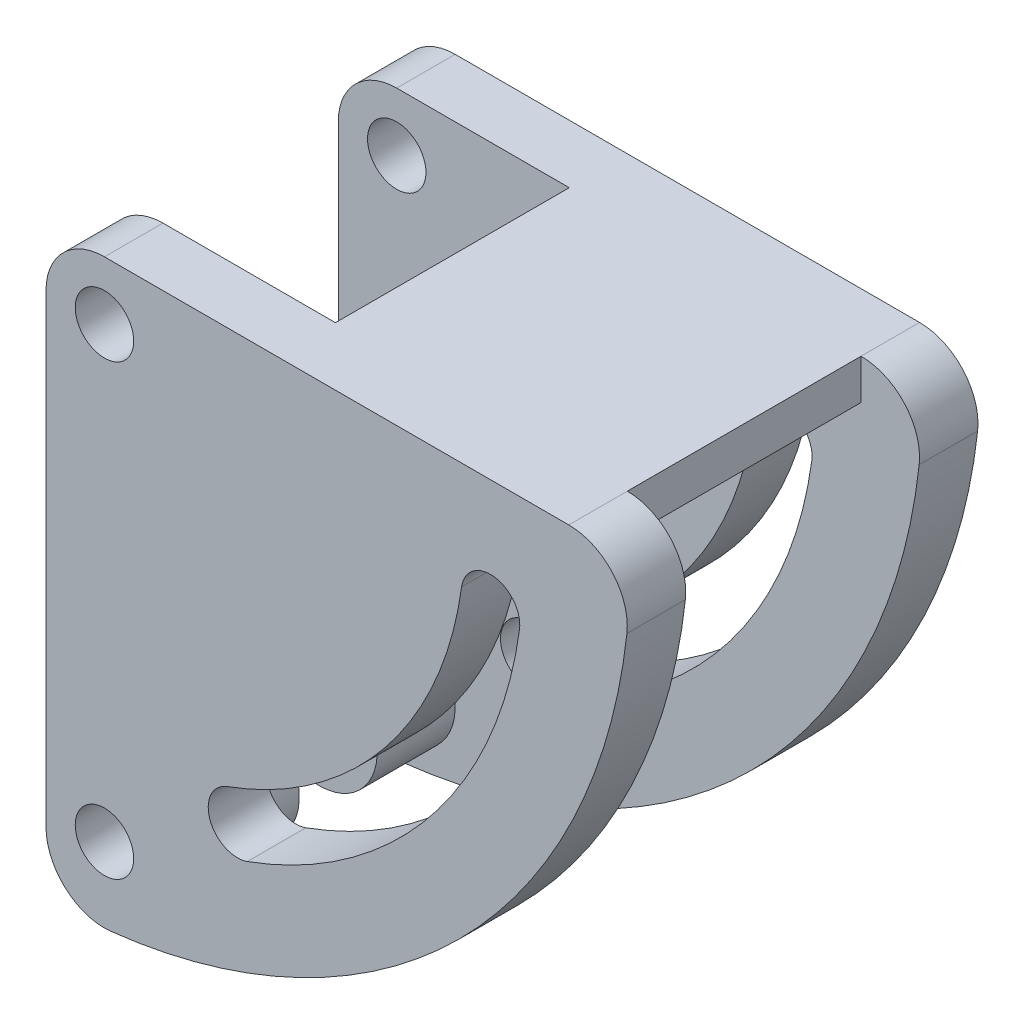
SolidWorks part; units mm, degrees
ref_plane "Front Plane" through (0, 0, 0) normal (0, 0, 1) x (1, 0, 0)
ref_plane "Top Plane" through (0, 0, 0) normal (0, 1, 0) x (1, 0, 0)
ref_plane "Right Plane" through (0, 0, 0) normal (1, 0, 0) x (0, 0, -1)
sketch "Sketch1" plane through (0, 0, 0) normal (0, 0, 1) x (1, 0, 0)
  line L0 (0, 0) -> (30, 0)
  line L1 (0, 0) -> (0, -30)
  arc A0 (0, -30) -> (30, 0) centre (0, 0) ccw
  circle A1 centre (3, -26) radius 1.5
  arc A4 (22.8157, -5.7086) -> (9.825, -21.7995) centre (3, -3) cw construction
  circle A7 centre (3, -3) radius 1.5
  arc A8 (21.3296, -5.5055) -> (9.3131, -20.3895) centre (3, -3) cw
  arc A9 (10.3369, -23.2094) -> (24.3019, -5.9118) centre (3, -3) ccw
  arc A10 (24.3019, -5.9118) -> (21.3296, -5.5055) centre (22.8157, -5.7086) ccw
  arc A11 (9.3131, -20.3895) -> (10.3369, -23.2094) centre (9.825, -21.7995) ccw
  point P7 (9.825, -21.7995)
  dimension "D2" = 3
  dimension "D3" = 3
  dimension "D8" = 30
  dimension "D1" = 20
  dimension "D4" = 3
  dimension "D5" = 3
  dimension "D6" = 4
  dimension "D7" = 3
extrude "Boss-Extrude1" add sketch "Sketch1" along normal blind 3
pattern_linear "LPattern1" count 2 spacing 15 along (0, 0, 1) of "Boss-Extrude1"
fillet "Fillet2" radius 3 3 edges at (0, -30, 1.5) (0, 0, 1.5) (30, 0, 1.5)
fillet "Fillet3" radius 3 3 edges at (0, -30, 16.5) (0, 0, 16.5) (30, 0, 16.5)
sketch "Sketch2" plane through (0, 0, 3) normal (0, 0, 1) x (1, 0, 0)
  line L0 (26.8328, 0) -> (3, 0) construction
  line L1 (11.8553, 0) -> (26.8328, 0)
  line L2 (11.8553, 0) -> (11.8553, -2.0588)
  line L3 (11.8553, -2.0588) -> (26.8328, -2.0588)
  line L4 (26.8328, 0) -> (26.8328, -2.0588)
extrude "Boss-Extrude2" add sketch "Sketch2" along normal up to next
sketch "Sketch3" plane through (0, 0, 15) normal (0, 0, -1) x (-1, 0, 0)
  circle A0 centre (-3, -26) radius 3
  circle A2 centre (-3, -26) radius 1.5
  circle A3 centre (-3, -26) radius 1.5 construction
  point P2 (-2.8603, -25.9262)
  point P6 (0, 0)
  dimension "D1" = 6
extrude "Boss-Extrude3" add sketch "Sketch3" along normal blind 4
pattern_linear "LPattern2" count 2 spacing 8 along (0, 0, -1) of "Boss-Extrude3"
